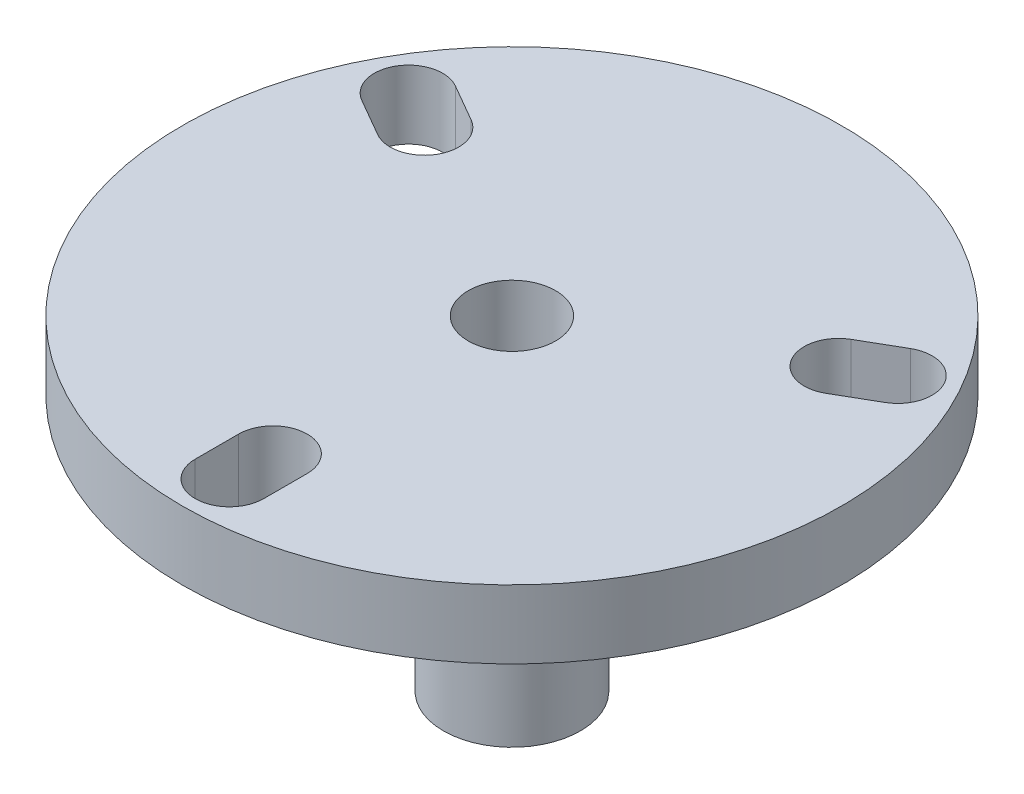
SolidWorks part; units mm, degrees
ref_plane "Front Plane" through (0, 0, 0) normal (0, 0, 1) x (1, 0, 0)
ref_plane "Top Plane" through (0, 0, 0) normal (0, 1, 0) x (1, 0, 0)
ref_plane "Right Plane" through (0, 0, 0) normal (1, 0, 0) x (0, 0, -1)
sketch "Sketch1" plane through (0, 0, 0) normal (0, 1, 0) x (1, 0, 0)
  line L0 (-2, -16.5) -> (-2, -13.96)
  line L1 (2, -16.5) -> (2, -13.96)
  line L2 (0, -16.5) -> (0, 0) construction
  line L3 (0, 0) -> (38.1669, 22.0357) construction
  line L4 (0, 0) -> (-43.0695, 24.8662) construction
  line L5 (-11.0897, 8.7121) -> (-13.0897, 5.2479) construction
  line L6 (-13.2894, 9.9821) -> (-15.2894, 6.5179) construction
  line L7 (11.0897, 8.7121) -> (13.0897, 5.2479) construction
  line L8 (13.2894, 9.9821) -> (15.2894, 6.5179) construction
  line L9 (13.0897, 5.2479) -> (15.2894, 6.5179)
  line L10 (13.2894, 9.9821) -> (11.0897, 8.7121)
  line L11 (-15.2894, 6.5179) -> (-13.0897, 5.2479)
  line L12 (-13.2894, 9.9821) -> (-11.0897, 8.7121)
  circle A0 centre (0, 0) radius 16.5
  circle A1 centre (0, 0) radius 19.25
  arc A2 (-1.9963, -16.3788) -> (1.9963, -16.3788) centre (0, -16.5) ccw
  arc A3 (2, -13.96) -> (-2, -13.96) centre (0, -13.96) ccw
  circle A4 centre (0, 0) radius 4
  arc A5 (15.1826, 6.4605) -> (13.1863, 9.9183) centre (14.2894, 8.25) ccw
  arc A6 (-13.1863, 9.9183) -> (-15.1826, 6.4605) centre (-14.2894, 8.25) ccw
  arc A7 (-13.0897, 5.2479) -> (-11.095, 8.7151) centre (-12.0897, 6.98) ccw
  arc A8 (11.0897, 8.7121) -> (13.0897, 5.2479) centre (12.0897, 6.98) ccw
  dimension "D1" = 38.5
  dimension "D2" = 33
  dimension "D3" = 4
  dimension "D5" = 8
  dimension "D8" = 4
  dimension "D9" = 4
  dimension "D10" = 4
  dimension "D11" = 4
  dimension "D4" = 2.54
  dimension "D6" = 120
  dimension "D7" = 120
  dimension "D12" = 2.54
  dimension "D15" = 2.54
extrude "Boss-Extrude1" add sketch "Sketch1" against normal blind 4 contours A1 A6 L12 A0 L10 A5 L9 L1 A2 L0 L11 | A8 L10 A0 L12 A7 L11 L0 A3 L1 L9 A4 region at (-13.886, 0, 8.0171) region at (-18.7055, 0, 0)
extrude "Boss-Extrude2" add sketch "Sketch1<4>" against normal blind 19 contours A4 region at (0, 0, 0)
sketch "Sketch1<4>" plane through (0, 0, 0) normal (0, 1, 0) x (1, 0, 0) same geometry as "Sketch1"
sketch "Sketch2" plane through (0, 0, 0) normal (1, 0, 0) x (0, 0, -1)
  line L0 (0, 0) -> (0, -19) construction
  line L1 (-4, -19) -> (4, -19) construction
  line L2 (0.8, -19) -> (0.8, -17)
  line L3 (1, 0) -> (0.8, -17)
  line L6 (19.25, 0) -> (-19.25, 0) construction
  line L7 (0, 0) -> (1, 0)
  line L8 (0, -19) -> (0.8, -19)
  line L9 (0, 0) -> (0, -19)
  line L10 (0, -19) -> (0.8, -19)
  dimension "D1" = 2
  dimension "D2" = 1
  dimension "D3" = 0.8
revolve "Cut-Revolve4" cut sketch "Sketch2" angle 360 about L0 region at (0, -9.1144, -0.4469)
ref_axis "Axis1" through (0, 0, 0) along (0, -1, 0)
sketch "Sketch5" plane through (0, 0, 0) normal (0, 0, 1) x (1, 0, 0)
  line L0 (0, 0) -> (0, -7) construction
  line L1 (0, -7) -> (-2.55, -5.5278)
  line L2 (-2.55, -5.5278) -> (-2.55, 0)
  line L3 (-2.55, 0) -> (0, 0)
  line L4 (1, 0) -> (-1, 0) construction
  line L5 (0, 0) -> (0, -7) construction
  line L6 (0, 0) -> (0, -7)
  dimension "D1" = 7
  dimension "D2" = 60
  dimension "D3" = 2.55
  dimension "D4" = 5.5278
revolve "Cut-Revolve8" cut sketch "Sketch5" angle 360 about axis through (0, 0, 0) along (0, -1, 0)
